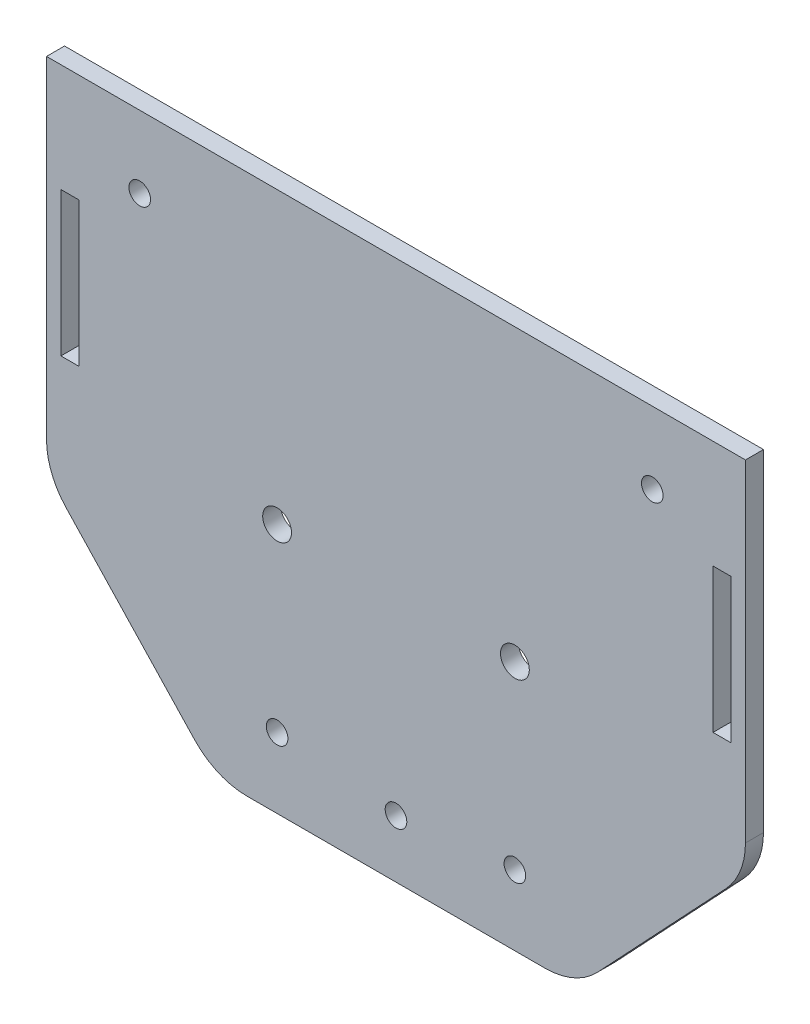
SolidWorks part; units mm, degrees
material "Maple"
ref_plane "Front Plane" through (0, 0, 0) normal (0, 0, 1) x (1, 0, 0)
ref_plane "Top Plane" through (0, 0, 0) normal (0, 1, 0) x (1, 0, 0)
ref_plane "Right Plane" through (0, 0, 0) normal (1, 0, 0) x (0, 0, -1)
sketch "Sketch1" plane through (0, 0, 0) normal (0, 0, 1) x (1, 0, 0)
  line L0 (48.5, 37.5) -> (-48.5, 37.5)
  line L1 (-48.5, -37.5) -> (48.5, -37.5) construction
  line L2 (-48.5, -37.5) -> (-48.5, 37.5) construction
  line L3 (-48.5, 37.5) -> (48.5, 37.5) construction
  line L4 (48.5, -37.5) -> (48.5, 37.5) construction
  line L5 (-48.5, -37.5) -> (48.5, 37.5) construction
  line L6 (-48.5, 37.5) -> (48.5, -37.5) construction
  line L7 (-48.5, 37.5) -> (-48.5, -12.5)
  line L8 (-48.5, -12.5) -> (-25, -37.5)
  line L9 (-25, -37.5) -> (25, -37.5)
  line L10 (0, 37.5) -> (0, -37.5) construction
  line L11 (-46.5, 22.5) -> (-44, 22.5)
  line L12 (-46.5, 22.5) -> (-46.5, 2.5)
  line L13 (-46.5, 2.5) -> (-44, 2.5)
  line L14 (-44, 22.5) -> (-44, 2.5)
  line L15 (-26.85, 7.5) -> (13.65, 7.5)
  line L16 (-26.85, 7.5) -> (-26.85, -13)
  line L17 (-26.85, -13) -> (13.65, -13)
  line L18 (13.65, 7.5) -> (13.65, -13)
  line L19 (48.5, -12.5) -> (25, -37.5)
  line L20 (48.5, 37.5) -> (48.5, -12.5)
  line L21 (46.5, 22.5) -> (44, 22.5)
  line L22 (46.5, 22.5) -> (46.5, 2.5)
  line L23 (46.5, 2.5) -> (44, 2.5)
  line L24 (44, 22.5) -> (44, 2.5)
  line L25 (-26.85, -2.75) -> (13.65, -2.75) construction
  line L26 (-6.6, 7.5) -> (-6.6, -13) construction
  circle A1 centre (0, -29.5) radius 1.5
  circle A2 centre (-16.5, -27.75) radius 1.5
  circle A3 centre (16.5, -27.75) radius 1.5
  circle A5 centre (-35.5667, 27.5) radius 1.5
  circle A6 centre (35.5667, 27.5) radius 1.5
  circle A7 centre (-29.5, 2.25) radius 1.5
  circle A8 centre (-29.5, -7.75) radius 1.5
  circle A9 centre (16.3, 2.25) radius 1.5
  circle A10 centre (16.3, -7.75) radius 1.5
  circle A11 centre (-16.5, -2.75) radius 2
  circle A12 centre (16.5, -2.75) radius 2
  point P0 (0, 0)
  point P14 (-46.5, 12.5)
  point P15 (-48.5, 12.5)
  point P29 (-26.85, -2.75)
  dimension "D14" = 3
  dimension "D17" = 10
  dimension "D18" = 45.8
  dimension "D19" = 3
  dimension "D22" = 4
  dimension "D1" = 97
  dimension "D2" = 75
  dimension "D3" = 50
  dimension "D4" = 25
  dimension "D5" = 2
  dimension "D6" = 2.5
  dimension "D7" = 20
  dimension "D8" = 30
  dimension "D9" = 40.5
  dimension "D10" = 20.5
  dimension "D11" = 10.35
  dimension "D12" = 33
  dimension "D13" = 25
  dimension "D15" = 8
  dimension "D16" = 10
  dimension "D20" = 9.75
  dimension "D21" = 71.1333
extrude "Boss-Extrude1" [suppressed] add sketch "Sketch1" along normal mid plane 2.5 contours L20 L0 L7 L8 L9 L19 A3 A2 A1 L24 L21 L22 L23 L11 L14 L13 L12 L15 L18 L17 L16 A5 A6 | A2 | A3 | A12
fillet "Fillet1" [suppressed] radius 10
extrude "Boss-Extrude2" add sketch "Sketch1<3>" along normal mid plane 2.5 contours L20 L0 L7 L8 L9 L19 A3 A2 A1 L24 L21 L22 L23 L11 L14 L13 L12 L15 L18 L17 L16 A5 A6 | L18 L15 L16 L17 | A7 | A8 | A10 | A9 region at (47.2739, 12.5, 0) region at (-6.4479, -2.75, 0)
sketch "Sketch1<3>" plane through (0, 0, 0) normal (0, 0, 1) x (1, 0, 0) same geometry as "Sketch1"
fillet "Fillet2" radius 10 4 edges at (48.5, -12.5, 0) (25, -37.5, 0) (-25, -37.5, 0) (-48.5, -12.5, 0)
